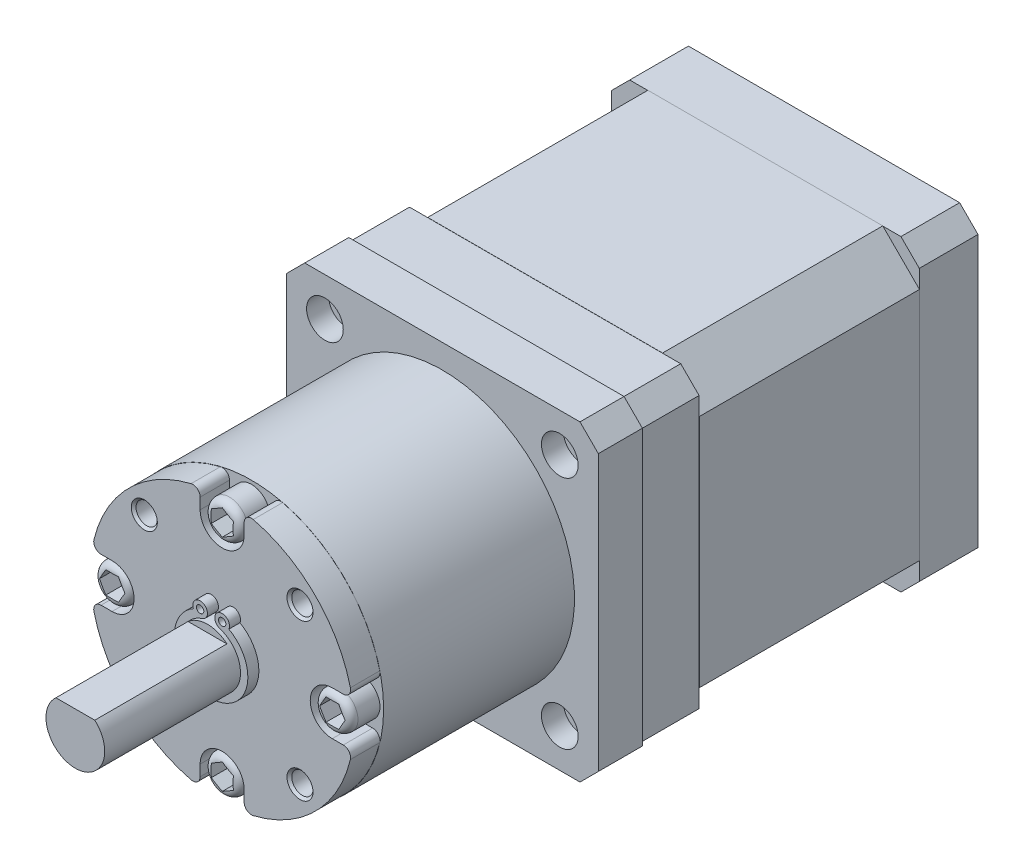
SolidWorks part; units mm, degrees
ref_plane "Front Plane" through (0, 0, 0) normal (0, 0, 1) x (1, 0, 0)
ref_plane "Top Plane" through (0, 0, 0) normal (0, 1, 0) x (1, 0, 0)
ref_plane "Right Plane" through (0, 0, 0) normal (1, 0, 0) x (0, 0, -1)
sketch "Sketch1" plane through (0, 0, 0) normal (0, 0, 1) x (1, 0, 0)
  line L1 (-21, 21) -> (21, 21)
  line L2 (-21, 21) -> (-21, -21)
  line L3 (-21, -21) -> (21, -21)
  line L4 (21, 21) -> (21, -21)
  line L5 (-21, 21) -> (21, -21) construction
  line L6 (-21, -21) -> (21, 21) construction
  point P0 (0, 0)
  dimension "D1" = 42
  dimension "D2" = 42
extrude "Boss-Extrude1" add sketch "Sketch1" along normal blind 30
chamfer "Chamfer1" distance 5 angle 45 4 edges at (-21, -21, 15) (-21, 21, 15) (21, -21, 15) (21, 21, 15)
ref_plane "Plane1" through (0, 0, 15) normal (0, 0, 1) x (1, 0, 0)
sketch "Sketch2" plane through (0, 0, 30) normal (0, 0, 1) x (1, 0, 0)
  line L1 (-20.975, 20.975) -> (20.975, 20.975)
  line L2 (-20.975, 20.975) -> (-20.975, -20.975)
  line L3 (-20.975, -20.975) -> (20.975, -20.975)
  line L4 (20.975, 20.975) -> (20.975, -20.975)
  line L5 (-20.975, 20.975) -> (20.975, -20.975) construction
  line L6 (-20.975, -20.975) -> (20.975, 20.975) construction
  point P0 (0, 0)
  dimension "D1" = 41.95
extrude "Boss-Extrude2" add sketch "Sketch2" along normal blind 8
mirror "Mirror1" about plane through (0, 0, 15) normal (0, 0, 1) of "Boss-Extrude2"
sketch "Sketch3" plane through (0, 0, 38) normal (0, 0, 1) x (1, 0, 0)
  circle A0 centre (0, 0) radius 18
  dimension "D1" = 36
extrude "Boss-Extrude3" add sketch "Sketch3" along normal blind 32
sketch "Sketch4" plane through (0, 0, -8) normal (0, 0, -1) x (-1, 0, 0)
  line L1 (-16, 16) -> (16, 16) construction
  line L2 (-16, 16) -> (-16, -16) construction
  line L3 (-16, -16) -> (16, -16) construction
  line L4 (16, 16) -> (16, -16) construction
  line L5 (-16, 16) -> (16, -16) construction
  line L6 (-16, -16) -> (16, 16) construction
  circle A0 centre (16, 16) radius 2
  circle A1 centre (16, -16) radius 2
  circle A2 centre (-16, -16) radius 2
  circle A3 centre (-16, 16) radius 2
  point P0 (0, 0)
  point P10 (0, 0)
  point P13 (0, 0)
  point P16 (0, 0)
  point P19 (0, 0)
  dimension "D2" = 4
  dimension "D4" = 16
  dimension "D1" = 32
  dimension "D3" = 4
extrude "Cut-Extrude1" cut sketch "Sketch4" against normal blind 1
sketch "Sketch5" plane through (0, 0, -7) normal (0, 0, -1) x (-1, 0, 0)
  line L0 (15.75, -14.5) -> (16.25, -14.5)
  line L1 (16.25, 14.5) -> (15.75, 14.5)
  line L2 (16.25, 14.5) -> (16.25, 17.5)
  line L3 (16.25, 17.5) -> (15.75, 17.5)
  line L4 (15.75, 14.5) -> (15.75, 17.5)
  line L5 (16.25, 14.5) -> (15.75, 17.5) construction
  line L6 (16.25, 17.5) -> (15.75, 14.5) construction
  line L7 (14.5, 15.75) -> (17.5, 15.75)
  line L8 (14.5, 15.75) -> (14.5, 16.25)
  line L9 (14.5, 16.25) -> (17.5, 16.25)
  line L10 (17.5, 15.75) -> (17.5, 16.25)
  line L11 (14.5, 15.75) -> (17.5, 16.25) construction
  line L12 (14.5, 16.25) -> (17.5, 15.75) construction
  line L13 (17.5, -16.25) -> (17.5, -15.75)
  line L14 (16.25, -14.5) -> (16.25, -17.5)
  line L15 (14.5, -15.75) -> (17.5, -15.75)
  line L16 (14.5, -16.25) -> (17.5, -16.25)
  line L17 (15.75, -14.5) -> (15.75, -17.5)
  line L18 (14.5, -16.25) -> (14.5, -15.75)
  line L19 (15.75, -17.5) -> (16.25, -17.5)
  line L20 (-14.5, -15.75) -> (-14.5, -16.25)
  line L21 (-16.25, -17.5) -> (-15.75, -17.5)
  line L22 (-14.5, -16.25) -> (-17.5, -16.25)
  line L23 (-15.75, -14.5) -> (-15.75, -17.5)
  line L24 (-16.25, -14.5) -> (-16.25, -17.5)
  line L25 (-14.5, -15.75) -> (-17.5, -15.75)
  line L26 (-16.25, -14.5) -> (-15.75, -14.5)
  line L27 (-17.5, -15.75) -> (-17.5, -16.25)
  line L28 (-15.75, 14.5) -> (-16.25, 14.5)
  line L29 (-17.5, 16.25) -> (-17.5, 15.75)
  line L30 (-16.25, 14.5) -> (-16.25, 17.5)
  line L31 (-14.5, 15.75) -> (-17.5, 15.75)
  line L32 (-14.5, 16.25) -> (-17.5, 16.25)
  line L33 (-15.75, 14.5) -> (-15.75, 17.5)
  line L34 (-14.5, 16.25) -> (-14.5, 15.75)
  line L35 (-15.75, 17.5) -> (-16.25, 17.5)
  point P0 (16, 16)
  point P6 (16, 16)
  point P38 (0, 0)
  dimension "D1" = 3
  dimension "D2" = 0.5
  dimension "D3" = 4
extrude "Cut-Extrude2" cut sketch "Sketch5" against normal blind 2 contours L4 L9 L2 L3 | L9 L8 L7 L4 | L9 L4 L7 L2 | L7 L4 L1 L2 | L7 L10 L9 L2 | L33 L35 L30 L32 | L31 L33 L32 L30 | L30 L32 L29 L31 | L34 L32 L33 L31 | L28 L33 L31 L30 | L26 L24 L25 L23 | L23 L25 L24 L22 | L22 L24 L21 L23 | L25 L27 L22 L24 | L20 L25 L23 L22 | L0 L17 L15 L14 | L15 L17 L16 L14 | L17 L19 L14 L16 | L14 L16 L13 L15 | L18 L16 L17 L15 | L25 L27 L22 L20 region at (-16, -15.125, -7) region at (-15.125, -16, -7) region at (-16, -16, -7) region at (-16.875, -16, -7) region at (-16, -16.875, -7) region at (-16, 15.125, -7) region at (-16, 16, -7) region at (-16.875, 16, -7) region at (-15.125, 16, -7) region at (-16, 16.875, -7) region at (15.125, -16, -7) region at (16, -15.125, -7) region at (16, -16, -7) region at (16, -16.875, -7) region at (16.875, -16, -7) region at (16, 15.125, -7) region at (15.125, 16, -7) region at (16, 16, -7) region at (16.875, 16, -7) region at (16, 16.875, -7)
sketch "Sketch6" plane through (0, 0, 38) normal (0, 0, 1) x (1, 0, 0)
  line L1 (-16, -16) -> (16, -16) construction
  line L2 (-16, -16) -> (-16, 16) construction
  line L3 (-16, 16) -> (16, 16) construction
  line L4 (16, -16) -> (16, 16) construction
  line L5 (-16, -16) -> (16, 16) construction
  line L6 (-16, 16) -> (16, -16) construction
  point P0 (0, 0)
  dimension "D1" = 32
sketch "Sketch10" plane through (0, 0, 70) normal (0, 0, 1) x (1, 0, 0)
  line L0 (-3, 15) -> (-3, 17.7229)
  line L1 (3, 15) -> (3, 17.7229)
  line L2 (15, 3) -> (17.7229, 3)
  line L3 (15, -3) -> (17.7229, -3)
  line L4 (3, -15) -> (3, -17.7229)
  line L5 (-3, -15) -> (-3, -17.7229)
  line L6 (-15, -3) -> (-17.7229, -3)
  line L7 (-15, 3) -> (-17.7229, 3)
  line L9 (-10.6066, -10.6066) -> (10.6066, -10.6066) construction
  line L10 (-10.6066, -10.6066) -> (-10.6066, 10.6066) construction
  line L11 (-10.6066, 10.6066) -> (10.6066, 10.6066) construction
  line L12 (10.6066, -10.6066) -> (10.6066, 10.6066) construction
  line L13 (-10.6066, -10.6066) -> (10.6066, 10.6066) construction
  line L14 (-10.6066, 10.6066) -> (10.6066, -10.6066) construction
  circle A0 centre (0, 0) radius 17.975
  circle A1 centre (0, 0) radius 15 construction
  arc A2 (-3, 15) -> (3, 15) centre (0, 15) ccw
  arc A6 (15, 3) -> (15, -3) centre (15, 0) ccw
  arc A7 (3, -15) -> (-3, -15) centre (0, -15) ccw
  arc A8 (-15, -3) -> (-15, 3) centre (-15, 0) ccw
  circle A9 centre (-10.6066, 10.6066) radius 2 construction
  circle A10 centre (10.6066, 10.6066) radius 2 construction
  circle A11 centre (10.6066, -10.6066) radius 2 construction
  circle A12 centre (-10.6066, -10.6066) radius 2 construction
  point P27 (0, 0)
  point P31 (0, 0)
  dimension "D1" = 35.95
  dimension "D2" = 30
  dimension "D3" = 6
  dimension "D6" = 4
  dimension "D5" = 30
  dimension "D4" = 4
extrude "Boss-Extrude4" add sketch "Sketch10" along normal blind 4 contours A8 L6 A0 L5 A7 L4 L3 A6 L2 L1 A2 L0 L7 A12 A11 A10 A9 region at (0, 0, 70)
fillet "Fillet2" radius 1 8 edges at (-3, -17.7229, 72) (3, -17.7229, 72) (-17.7229, -3, 72) (-17.7229, 3, 72) (3, 17.7229, 72) (-3, 17.7229, 72) (17.7229, -3, 72) (17.7229, 3, 72)
sketch "Sketch11" plane through (0, 0, 74) normal (0, 0, 1) x (1, 0, 0)
  circle A0 centre (0, 0) radius 4
  dimension "D1" = 8
extrude "Boss-Extrude5" add sketch "Sketch11" along normal blind 20
sketch "Sketch12" plane through (0, 0, 94) normal (0, 0, 1) x (1, 0, 0)
  line L0 (0, 0) -> (0, 4) construction
  line L1 (-2.6458, 3) -> (2.6458, 3)
  circle A0 centre (0, 0) radius 4
  circle M2 centre (0, 0) radius 4
  dimension "D1" = 8
  dimension "D2" = 3
extrude "Cut-Extrude3" cut sketch "Sketch12" against normal blind 18 contours L0 L1 M2 | L1 L0 A0 region at (-1.0111, 3.4046, 94) region at (1.0111, 3.4046, 94)
sketch "Sketch13" plane through (0, 0, 38) normal (0, 0, 1) x (1, 0, 0)
  line L1 (-21.25, -21.25) -> (21.25, -21.25)
  line L2 (-21.25, -21.25) -> (-21.25, 21.25)
  line L3 (-21.25, 21.25) -> (21.25, 21.25)
  line L4 (21.25, -21.25) -> (21.25, 21.25)
  line L5 (-21.25, -21.25) -> (21.25, 21.25) construction
  line L6 (-21.25, 21.25) -> (21.25, -21.25) construction
  point P0 (0, 0)
  dimension "D1" = 42.5
extrude "Boss-Extrude6" add sketch "Sketch13" along normal blind 6
hole_wizard "M3.5 Tapped Hole4" positions "Sketch17" profile "Sketch18" tap size "M3.5" standard "ISO"
sketch "Sketch17" plane through (0, 0, 74) normal (0, 0, 1) x (1, 0, 0)
  point P0 (-10.6066, 10.6066)
  point P3 (10.6066, 10.6066)
  point P6 (10.6066, -10.6066)
  point P9 (-10.6066, -10.6066)
sketch "Sketch18" plane through (-10.6066, 10.6066, 74) normal (1, 0, 0) x (0, -1, 0)
  line L0 (0, 0) -> (0, 6.6712)
  line L1 (0, 6.6712) -> (1.45, 5.8)
  line L2 (1.45, 5.8) -> (1.45, 0.325)
  line L3 (1.45, 0.325) -> (1.775, 0)
  line L5 (1.775, 0) -> (0, 0)
  line L6 (-1.45, 0.325) -> (-1.775, 0) construction
  line L10 (0, 6.6712) -> (-1.45, 5.8) construction
  line L11 (0, -6.35) -> (0, 107.95) construction
  dimension "Tap Drill Dia." = 2.9
  dimension "Tap Drill Depth" = 5.8
  dimension "Near C'Sink Dia." = 3.55
  dimension "Near C'Sink Angle" = 90
  dimension "Drill Angle" = 118
cosmetic thread "Hole Thread5" parameters "D1"=4, "D2"=3.5
cosmetic thread "Hole Thread6" parameters "D1"=4, "D2"=3.5
cosmetic thread "Hole Thread7" parameters "D1"=4, "D2"=3.5
cosmetic thread "Hole Thread8" parameters "D1"=4, "D2"=3.5
sketch "Sketch19" plane through (0, 0, 70) normal (0, 0, 1) x (1, 0, 0)
  line L0 (16.7321, 0) -> (15.866, 1.5)
  line L1 (0, 16.7321) -> (-1.5, 15.866)
  line L2 (-1.5, 15.866) -> (-1.5, 14.134)
  line L3 (-1.5, 14.134) -> (0, 13.2679)
  line L4 (0, 13.2679) -> (1.5, 14.134)
  line L5 (1.5, 14.134) -> (1.5, 15.866)
  line L6 (1.5, 15.866) -> (0, 16.7321)
  line L7 (15.866, 1.5) -> (14.134, 1.5)
  line L8 (14.134, 1.5) -> (13.2679, 0)
  line L9 (13.2679, 0) -> (14.134, -1.5)
  line L10 (14.134, -1.5) -> (15.866, -1.5)
  line L11 (15.866, -1.5) -> (16.7321, 0)
  line L12 (0, -16.7321) -> (1.5, -15.866)
  line L13 (1.5, -15.866) -> (1.5, -14.134)
  line L14 (1.5, -14.134) -> (0, -13.2679)
  line L15 (0, -13.2679) -> (-1.5, -14.134)
  line L16 (-1.5, -14.134) -> (-1.5, -15.866)
  line L17 (-1.5, -15.866) -> (0, -16.7321)
  line L18 (-16.7321, 0) -> (-15.866, -1.5)
  line L19 (-15.866, -1.5) -> (-14.134, -1.5)
  line L20 (-14.134, -1.5) -> (-13.2679, 0)
  line L21 (-13.2679, 0) -> (-14.134, 1.5)
  line L22 (-14.134, 1.5) -> (-15.866, 1.5)
  line L23 (-15.866, 1.5) -> (-16.7321, 0)
  circle A0 centre (0, 0) radius 15 construction
  circle A1 centre (0, 15) radius 1.5 construction
  circle A2 centre (0, 15) radius 2.5
  circle A3 centre (15, 0) radius 2.5
  circle A4 centre (0, -15) radius 2.5
  circle A5 centre (-15, 0) radius 2.5
  point P33 (0, 0)
  point P41 (0, 0)
  dimension "D1" = 3
  dimension "D2" = 4
  dimension "D3" = 5
  dimension "D4" = 4
extrude "Boss-Extrude7" add sketch "Sketch19" along normal up to surface (4 mm away) contours A2 | L1 L2 L3 L4 L5 L6 | A3 | L0 L7 L8 L9 L10 L11 | A4 | L12 L13 L14 L15 L16 L17 | A5 | L18 L19 L20 L21 L22 L23 up to face at (-8.8316, 10.6066, 74)
fillet "Fillet4" radius 1 4 edges at (2.5, -15, 74) (-12.5, 0, 74) (17.5, 0, 74) (2.5, 15, 74)
sketch "Sketch20" plane through (0, 0, 74) normal (0, 0, 1) x (1, 0, 0)
  line L0 (0, 0) -> (0, 4) construction
  line L1 (-1.5, 4.7697) -> (1.5, 4.7697) construction
  arc A0 (-1.2, 3.8158) -> (1.2, 3.8158) centre (0, 0) ccw
  arc A1 (-2.4192, 4.3758) -> (2.4192, 4.3758) centre (0, 0) ccw
  arc A2 (-1.2, 3.8158) -> (-2.4192, 4.3758) centre (-1.5, 4.7697) ccw
  arc A3 (2.4192, 4.3758) -> (1.2, 3.8158) centre (1.5, 4.7697) ccw
  circle A4 centre (1.5, 4.7697) radius 0.5
  circle A5 centre (-1.5, 4.7697) radius 0.5
  point P8 (0, 4.7697)
  dimension "D2" = 10
  dimension "D3" = 8
  dimension "D4" = 1
  dimension "D1" = 3
extrude "Boss-Extrude8" add sketch "Sketch20" along normal blind 1.5 contours A2 A1 A3 A0 | A4 | A5
sketch "Sketch21" plane through (0, -21, 0) normal (0, -1, 0) x (1, 0, 0)
  line L0 (0, 0) -> (0, -8) construction
  line L1 (-4.5, -2.5) -> (4.5, -2.5)
  line L2 (-4.5, -2.5) -> (-4.5, -5.5)
  line L3 (-4.5, -5.5) -> (4.5, -5.5)
  line L4 (4.5, -2.5) -> (4.5, -5.5)
  line L5 (-4.5, -2.5) -> (4.5, -5.5) construction
  line L6 (-4.5, -5.5) -> (4.5, -2.5) construction
  line L7 (-3, -3) -> (3, -3)
  line L8 (-3, -3) -> (-3, -5)
  line L9 (-3, -5) -> (3, -5)
  line L10 (3, -3) -> (3, -5)
  line L11 (-3, -3) -> (3, -5) construction
  line L12 (-3, -5) -> (3, -3) construction
  line L13 (-20.975, -8) -> (20.975, -8) construction
  point P0 (0, -4)
  point P5 (0, -4)
  dimension "D1" = 6
  dimension "D2" = 2
  dimension "D3" = 4
  dimension "D4" = 0.5
extrude "Boss-Extrude9" add sketch "Sketch21" along normal blind 1 contours L2 L1 L4 L3 | L8 L7 L10 L9
sketch "Sketch22" plane through (0, -21, 0) normal (0, -1, 0) x (1, 0, 0)
  line L0 (3, -4) -> (1.8, -4) construction
  line L1 (3, -3) -> (3, -5) construction
  circle A0 centre (2.3, -4) radius 0.5
  dimension "D1" = 1
  dimension "D2" = 0.7
extrude "Boss-Extrude10" add sketch "Sketch22" along normal blind 5
sketch "Sketch23" plane through (0, -21, 0) normal (0, -1, 0) x (1, 0, 0)
  line L0 (3, -4) -> (-2.8, -4) construction
  line L1 (3, -3) -> (3, -5) construction
  line L3 (0, -2.983) -> (0, -4.8148) construction
  circle A0 centre (0.7, -4) radius 0.5
  circle A1 centre (2.3, -4) radius 0.5
  circle A2 centre (-2.3, -4) radius 0.5
  circle A3 centre (-0.7, -4) radius 0.5
  dimension "D2" = 1
  dimension "D3" = 1
  dimension "D1" = 0.7
extrude "Boss-Extrude11" add sketch "Sketch23" along normal blind 5
chamfer "Chamfer4" distance 2.5 angle 45 12 edges at (20.975, 20.975, -4) (-20.975, 20.975, -4) (-20.975, -20.975, -4) (20.975, -20.975, -4) (20.975, -20.975, 34) (21.25, -21.25, 41) (20.975, 20.975, 34) (21.25, 21.25, 41) (-21.25, 21.25, 41) (-20.975, 20.975, 34) (-20.975, -20.975, 34) (-21.25, -21.25, 41)
sketch "Sketch24" plane through (0, 0, 44) normal (0, 0, 1) x (1, 0, 0)
  line L1 (-16, -16) -> (16, -16) construction
  line L2 (-16, -16) -> (-16, 16) construction
  line L3 (-16, 16) -> (16, 16) construction
  line L4 (16, -16) -> (16, 16) construction
  line L5 (-16, -16) -> (16, 16) construction
  line L6 (-16, 16) -> (16, -16) construction
  circle A0 centre (-16, 16) radius 2.5
  circle A1 centre (16, 16) radius 2.5
  circle A2 centre (16, -16) radius 2.5
  circle A3 centre (-16, -16) radius 2.5
  point P0 (0, 0)
  dimension "D2" = 5
  dimension "D1" = 32
extrude "Cut-Extrude4" cut sketch "Sketch24" against normal blind 3
sketch "Sketch25" plane through (0, 0, 41) normal (0, 0, 1) x (1, 0, 0)
  line L0 (14, 15.5) -> (18, 15.5)
  line L1 (-15.5, 14) -> (-16.5, 14)
  line L2 (-15.5, 14) -> (-15.5, 18)
  line L3 (-15.5, 18) -> (-16.5, 18)
  line L4 (-16.5, 14) -> (-16.5, 18)
  line L5 (-15.5, 14) -> (-16.5, 18) construction
  line L6 (-15.5, 18) -> (-16.5, 14) construction
  line L7 (-18, 16.5) -> (-14, 16.5)
  line L8 (-18, 16.5) -> (-18, 15.5)
  line L9 (-18, 15.5) -> (-14, 15.5)
  line L10 (-14, 16.5) -> (-14, 15.5)
  line L11 (-18, 16.5) -> (-14, 15.5) construction
  line L12 (-18, 15.5) -> (-14, 16.5) construction
  line L13 (14, 15.5) -> (14, 16.5)
  line L14 (14, 16.5) -> (18, 16.5)
  line L15 (18, 15.5) -> (18, 16.5)
  line L16 (16.5, 18) -> (15.5, 18)
  line L17 (16.5, 18) -> (16.5, 14)
  line L18 (16.5, 14) -> (15.5, 14)
  line L19 (15.5, 18) -> (15.5, 14)
  line L20 (15.5, -14) -> (15.5, -18)
  line L21 (15.5, -14) -> (16.5, -14)
  line L22 (16.5, -14) -> (16.5, -18)
  line L23 (15.5, -18) -> (16.5, -18)
  line L24 (18, -16.5) -> (18, -15.5)
  line L25 (18, -16.5) -> (14, -16.5)
  line L26 (14, -16.5) -> (14, -15.5)
  line L27 (18, -15.5) -> (14, -15.5)
  line L28 (-14, -15.5) -> (-18, -15.5)
  line L29 (-14, -15.5) -> (-14, -16.5)
  line L30 (-14, -16.5) -> (-18, -16.5)
  line L31 (-18, -15.5) -> (-18, -16.5)
  line L32 (-16.5, -18) -> (-15.5, -18)
  line L33 (-16.5, -18) -> (-16.5, -14)
  line L34 (-16.5, -14) -> (-15.5, -14)
  line L35 (-15.5, -18) -> (-15.5, -14)
  point P0 (-16, 16)
  point P6 (-16, 16)
  point P38 (0, 0)
  dimension "D1" = 1
  dimension "D2" = 4
  dimension "D3" = 4
extrude "Cut-Extrude5" cut sketch "Sketch25" against normal blind 2 contours L4 L7 L2 L3 | L4 L9 L2 L7 | L8 L9 L4 L7 | L10 L7 L2 L9 | L9 L4 L1 L2 | L16 L19 L14 L17 | L19 L14 L13 L0 | L14 L19 L0 L17 | L14 L17 L0 L15 | L0 L19 L18 L17 | L27 L22 L21 L20 | L22 L27 L20 L25 | L24 L27 L22 L25 | L20 L27 L26 L25 | L22 L25 L20 L23 | L28 L35 L34 L33 | L30 L35 L28 L33 | L35 L30 L29 L28 | L30 L33 L28 L31 | L32 L35 L30 L33 region at (14.75, 16, 41) region at (16, 16, 41) region at (16, 14.75, 41) region at (17.25, 16, 41) region at (16, 17.25, 41) region at (-16, 14.75, 41) region at (-16, 16, 41) region at (-14.75, 16, 41) region at (-17.25, 16, 41) region at (-16, 17.25, 41) region at (16, -14.75, 41) region at (16, -16, 41) region at (14.75, -16, 41) region at (16, -17.25, 41) region at (17.25, -16, 41) region at (-14.75, -16, 41) region at (-16, -16, 41) region at (-16, -14.75, 41) region at (-17.25, -16, 41) region at (-16, -17.25, 41)
